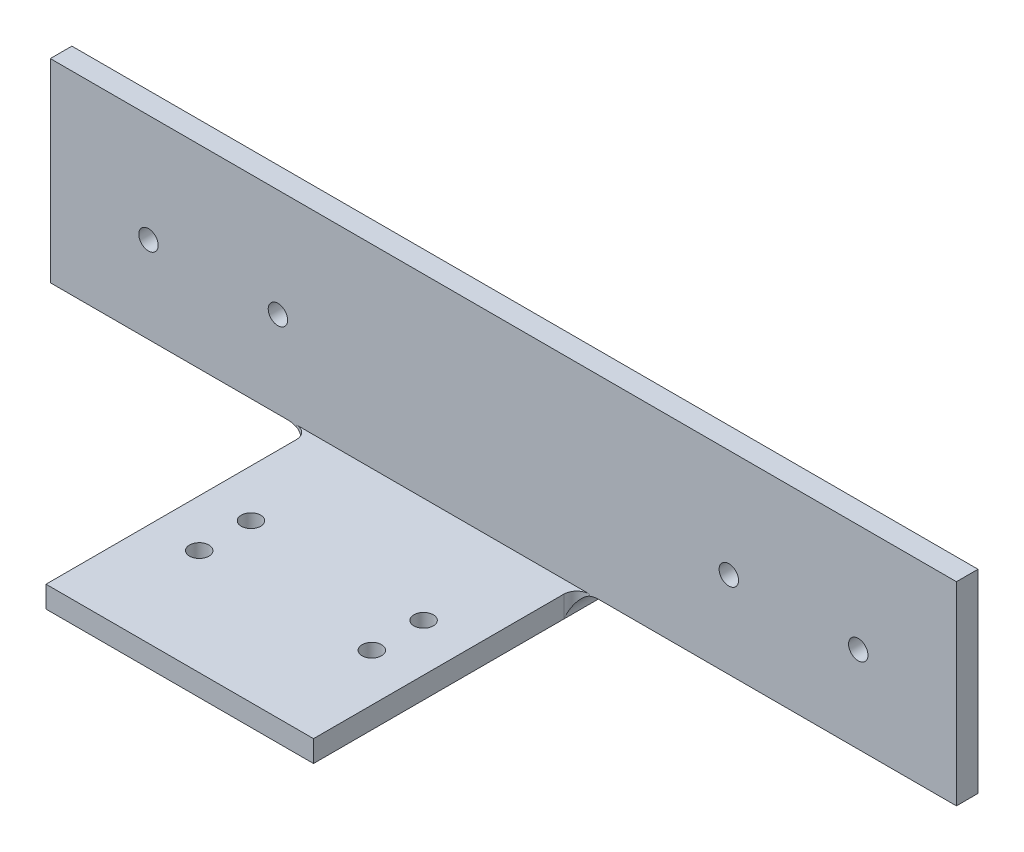
SolidWorks part; units mm, degrees
ref_plane "前视基准面" through (0, 0, 0) normal (0, 0, 1) x (1, 0, 0)
ref_plane "上视基准面" through (0, 0, 0) normal (0, 1, 0) x (1, 0, 0)
ref_plane "右视基准面" through (0, 0, 0) normal (1, 0, 0) x (0, 0, -1)
other "Configuration Table"
sketch "草图1" plane through (0, 0, 0) normal (0, 0, 1) x (1, 0, 0)
  line L1 (0, 0) -> (210, 0)
  line L2 (0, 0) -> (0, 50)
  line L3 (0, 50) -> (210, 50)
  line L4 (210, 0) -> (210, 50)
  line L5 (0, 0) -> (210, 50) construction
  line L6 (0, 50) -> (210, 0) construction
  point P4 (105, 25)
  dimension "D1" = 210
  dimension "D2" = 50
extrude "凸台-拉伸1" add sketch "草图1" along normal blind 5
sketch "草图2" plane through (0, 0, 5) normal (0, 0, 1) x (1, 0, 0)
  line L0 (150, 50) -> (150, 0) construction
  line L1 (210, 50) -> (0, 50) construction
  line L2 (0, 0) -> (210, 0) construction
  line L7 (0, 50) -> (0, 0)
  line L8 (0, 0) -> (210, 0)
  line L9 (210, 0) -> (210, 50)
  line L10 (210, 50) -> (0, 50)
  line L11 (0, 50) -> (0, 0) construction
  line L12 (0, 0) -> (210, 0) construction
  line L13 (210, 0) -> (210, 50) construction
  line L14 (210, 50) -> (0, 50) construction
  dimension "D2" = 60
  dimension "D1" = 0
sketch "草图3" plane through (0, 0, 5) normal (0, 0, 1) x (1, 0, 0)
  line L0 (172.25, 50) -> (172.25, 0) construction
  line L1 (12, 50) -> (198, 50) construction
  line L2 (12, 50) -> (12, 0) construction
  line L3 (12, 0) -> (198, 0) construction
  line L4 (0, 50) -> (0, 0)
  line L5 (0, 0) -> (210, 0)
  line L6 (210, 0) -> (210, 50)
  line L7 (210, 50) -> (0, 50)
  line L8 (0, 50) -> (0, 0) construction
  line L9 (0, 0) -> (210, 0) construction
  line L10 (210, 0) -> (210, 50) construction
  line L11 (210, 50) -> (0, 50) construction
  line L12 (198, 50) -> (198, 0) construction
  line L13 (12, 50) -> (198, 0) construction
  line L14 (12, 0) -> (198, 50) construction
  line L15 (198, 50) -> (146.5, 50) construction
  line L16 (198, 50) -> (198, 0) construction
  line L17 (198, 0) -> (146.5, 0) construction
  line L18 (146.5, 50) -> (146.5, 0) construction
  line L19 (198, 50) -> (146.5, 0) construction
  line L20 (198, 0) -> (146.5, 50) construction
  line L21 (198, 50) -> (194, 50)
  line L22 (198, 50) -> (198, 0) construction
  line L23 (198, 0) -> (194, 0)
  line L24 (194, 50) -> (194, 0) construction
  line L25 (198, 50) -> (194, 0) construction
  line L26 (198, 0) -> (194, 50) construction
  line L27 (157.25, 25) -> (187.25, 25) construction
  line L28 (105, 50) -> (105, 0) construction
  line L29 (52.75, 25) -> (22.75, 25) construction
  circle A0 centre (157.25, 25) radius 2.25
  circle A1 centre (187.25, 25) radius 2.25
  circle A2 centre (22.75, 25) radius 2.25
  circle A3 centre (52.75, 25) radius 2.25
  point P8 (105, 25)
  point P11 (172.25, 25)
  point P14 (196, 25)
  point P21 (172.25, 25)
  point P28 (14, 25)
  point P29 (37.75, 25)
  dimension "D7" = 4.5
  dimension "D8" = 4.5
  dimension "D2" = 105
  dimension "D3" = 186
  dimension "D4" = 51.5
  dimension "D5" = 4
  dimension "D6" = 30
  dimension "D9" = 25
  dimension "D1" = 0
extrude "切除-拉伸1" cut sketch "草图3" against normal blind 5 contours A2 | A3 | A0 | A1
sketch "草图4" plane through (0, 0, 5) normal (0, 0, 1) x (1, 0, 0)
  line L0 (0, 50) -> (0, 0) construction
  line L1 (210, 0) -> (0, 0)
  line L2 (210, 0) -> (210, 5)
  line L3 (210, 5) -> (0, 5)
  line L4 (0, 0) -> (0, 5)
  line L5 (210, 0) -> (0, 5) construction
  line L6 (210, 5) -> (0, 0) construction
  point P4 (105, 2.5)
  dimension "D1" = 5
extrude "凸台-拉伸2" add sketch "草图4" along normal blind 61
sketch "草图6" plane through (0, 0, 66) normal (0, 0, 1) x (1, 0, 0)
  line L0 (0, 0) -> (210, 0) construction
  line L1 (210, 5) -> (150, 5)
  line L2 (210, 5) -> (210, 0)
  line L3 (210, 0) -> (150, 0)
  line L4 (150, 5) -> (150, 0)
  line L5 (210, 5) -> (150, 0) construction
  line L6 (210, 0) -> (150, 5) construction
  point P4 (180, 2.5)
  dimension "D1" = 60
extrude "切除-拉伸2" cut sketch "草图6" against normal up to next
fillet "圆角1" radius 10 1 edges at (150, 5, 2.5)
sketch "草图7" plane through (0, 0, 66) normal (0, 0, 1) x (1, 0, 0)
  line L0 (0, 0) -> (210, 0) construction
  line L1 (150, 5) -> (91, 5) construction
  line L2 (150, 5) -> (150, 0)
  line L3 (150, 0) -> (91, 0) construction
  line L4 (91, 5) -> (91, 0) construction
  line L5 (150, 5) -> (91, 0) construction
  line L6 (150, 0) -> (91, 5) construction
  line L8 (0, 5) -> (88, 5)
  line L9 (0, 5) -> (0, 0)
  line L10 (0, 0) -> (88, 0)
  line L11 (88, 5) -> (88, 0)
  line L12 (0, 5) -> (88, 0) construction
  line L13 (0, 0) -> (88, 5) construction
  point P4 (120.5, 2.5)
  point P13 (44, 2.5)
  line M6 (150, 5) -> (0, 5)
  line M7 (0, 5) -> (0, 0)
  line M8 (0, 0) -> (150, 0)
  dimension "D1" = 59
  dimension "D2" = 3
extrude "切除-拉伸3" cut sketch "草图7" against normal up to next contours L11 M6 M7 M8 region at (44, 2.5, 66)
fillet "圆角2" radius 10 1 edges at (88, 5, 2.5)
fillet "圆角6" radius 3 2 edges at (88, 2.5, 5) (150, 2.5, 5)
sketch "草图11" plane through (0, 5, 0) normal (0, 1, 0) x (1, 0, 0)
  line L0 (210, -5) -> (0, -5) construction
  line L1 (88, -66) -> (149.9823, -66)
  line L2 (88, -66) -> (88, -5) construction
  line L3 (88, -5) -> (149.9823, -5)
  line L4 (149.9823, -66) -> (149.9823, -5) construction
  line L5 (88, -66) -> (149.9823, -5) construction
  line L6 (88, -5) -> (149.9823, -66) construction
  line L8 (88, -5) -> (149.9823, -5)
  line L9 (88, -5) -> (88, -6)
  line L10 (88, -6) -> (149.9823, -6)
  line L11 (149.9823, -5) -> (149.9823, -6)
  line L12 (88, -5) -> (149.9823, -6) construction
  line L13 (88, -6) -> (149.9823, -5) construction
  line L14 (88, -6) -> (91, -6)
  line L15 (88, -6) -> (88, -66)
  line L16 (88, -66) -> (91, -66)
  line L17 (91, -6) -> (91, -66) construction
  line L18 (88, -6) -> (91, -66) construction
  line L19 (88, -66) -> (91, -6) construction
  line L20 (149.9823, -6) -> (146.9823, -6)
  line L21 (149.9823, -6) -> (149.9823, -66)
  line L22 (149.9823, -66) -> (146.9823, -66)
  line L23 (146.9823, -6) -> (146.9823, -66) construction
  line L24 (149.9823, -6) -> (146.9823, -66) construction
  line L25 (149.9823, -66) -> (146.9823, -6) construction
  line L26 (138.9912, -41.5) -> (98.9912, -41.5) construction
  line L27 (138.9912, -41.5) -> (138.9912, -29.5) construction
  line L28 (138.9912, -29.5) -> (98.9912, -29.5) construction
  line L29 (98.9912, -41.5) -> (98.9912, -29.5) construction
  line L30 (138.9912, -41.5) -> (98.9912, -29.5) construction
  line L31 (138.9912, -29.5) -> (98.9912, -41.5) construction
  circle A0 centre (98.9912, -41.5) radius 2.25
  circle A1 centre (98.9912, -29.5) radius 2.25
  circle A2 centre (138.9912, -29.5) radius 2.25
  circle A3 centre (138.9912, -41.5) radius 2.25
  point P4 (118.9912, -35.5)
  point P10 (118.9912, -5.5)
  point P13 (89.5, -36)
  point P16 (148.4823, -36)
  point P17 (118.9912, -35.5)
  dimension "D7" = 4.5
  dimension "D1" = 61.9823
  dimension "D2" = 1
  dimension "D3" = 3
  dimension "D4" = 3
  dimension "D5" = 40
  dimension "D6" = 12
extrude "切除-拉伸4" cut sketch "草图11" against normal through all contours A1 | A2 | A0 | A3 region at (98.9912, 5, 41.5) region at (98.9912, 5, 29.5) region at (138.9912, 5, 29.5) region at (138.9912, 5, 41.5)
ref_plane "基准面1" through (220, 0, 0) normal (1, 0, 0) x (0, 0, -1)
mirror "镜向16" about plane through (210, 0, 5) normal (-1, 0, 0) of "切除-拉伸4", "切除-拉伸3", "切除-拉伸2", "凸台-拉伸2", "切除-拉伸1", "凸台-拉伸1"
sketch "草图14" plane through (0, 0, 5) normal (0, 0, 1) x (1, 0, 0)
  line L0 (210, 50) -> (210, 0)
split "分割2" trim tools "草图14" bodies to split 120 resulting bodies 122
fillet "圆角8" radius 5 2 edges at (332, 5, 2.5) (270, 5, 2.5)
fillet "圆角9" radius 3 2 edges at (270, 2.5, 5) (332, 2.5, 5)
